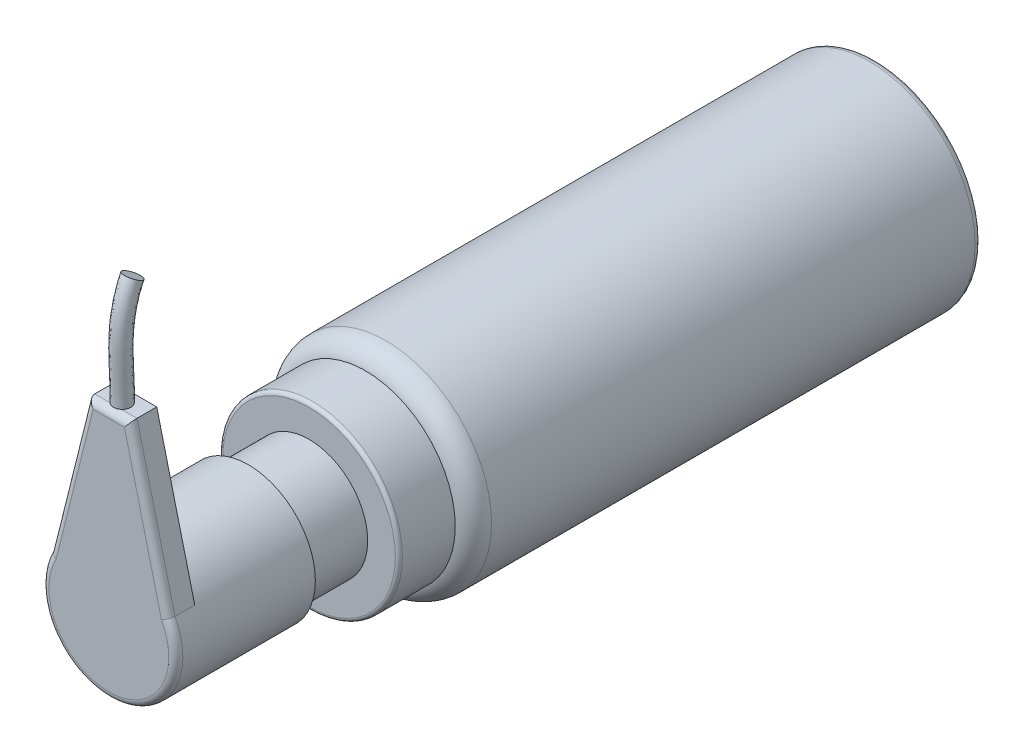
SolidWorks part; units mm, degrees
ref_plane "Front Plane" through (0, 0, 0) normal (0, 0, 1) x (1, 0, 0)
ref_plane "Top Plane" through (0, 0, 0) normal (0, 1, 0) x (1, 0, 0)
ref_plane "Right Plane" through (0, 0, 0) normal (1, 0, 0) x (0, 0, -1)
sketch "Sketch1" plane through (0, 0, 0) normal (0, 0, 1) x (1, 0, 0)
  circle A0 centre (0, 0) radius 30
extrude "Boss-Extrude1" add sketch "Sketch1" along normal blind 145
sketch "Sketch2" plane through (0, 0, 145) normal (0, 0, 1) x (1, 0, 0)
  circle A0 centre (0, 0) radius 25.5
  dimension "D1" = 51
extrude "Boss-Extrude2" add sketch "Sketch2" along normal blind 16
sketch "Sketch3" plane through (0, 0, 161) normal (0, 0, 1) x (1, 0, 0)
  circle A0 centre (0, 0) radius 16.65
  dimension "D1" = 33.3
extrude "Boss-Extrude3" add sketch "Sketch3" along normal blind 17.2 contours A0
sketch "Sketch4" plane through (0, 0, 178.2) normal (0, 0, 1) x (1, 0, 0)
  circle A0 centre (0, 0) radius 19
  dimension "D1" = 38
extrude "Boss-Extrude4" add sketch "Sketch4" along normal blind 32
sketch "Sketch5" plane through (0, 0, 210.2) normal (0, 0, 1) x (1, 0, 0)
  line L1 (-6, 52.2) -> (6, 52.2)
  line L2 (16.7808, 8.9109) -> (6, 52.2)
  line L3 (-16.7808, 8.9109) -> (-6, 52.2)
  arc A0 (-16.7808, 8.9109) -> (16.7808, 8.9109) centre (0, 0) ccw
  point P7 (0, 52.2)
  dimension "D2" = 12
extrude "Boss-Extrude5" add sketch "Sketch5" along normal blind 7.6
sketch "Sketch6" plane through (0, 0, 0) normal (1, 0, 0) x (0, 0, -1)
  line L1 (-217.8, 52.2) -> (-210.2, 52.2) construction
  spline S0 degree 3 poles (-214, 52.2) (-213.8668, 62.1146) (-216.0525, 71.7072) (-211.0831, 81.9383) knots 0 0 0 0 1 1 1 1
  point P1 (-211.0831, 81.9383)
sweep "Sweep1" add path "Sketch6" circular profile diameter 4.9 parameters "D3"=4.9
fillet "Fillet1" radius 6 1 edges at (30, 0, 145)
fillet "Fillet2" radius 1 1 edges at (25.5, 0, 161)
fillet "Fillet3" radius 2 1 edges at (30, 0, 0)
fillet "Fillet4" radius 2 4 edges at (0, -19, 217.8) (-11.3904, 30.5555, 217.8) (0, 52.2, 217.8) (11.3904, 30.5555, 217.8)
